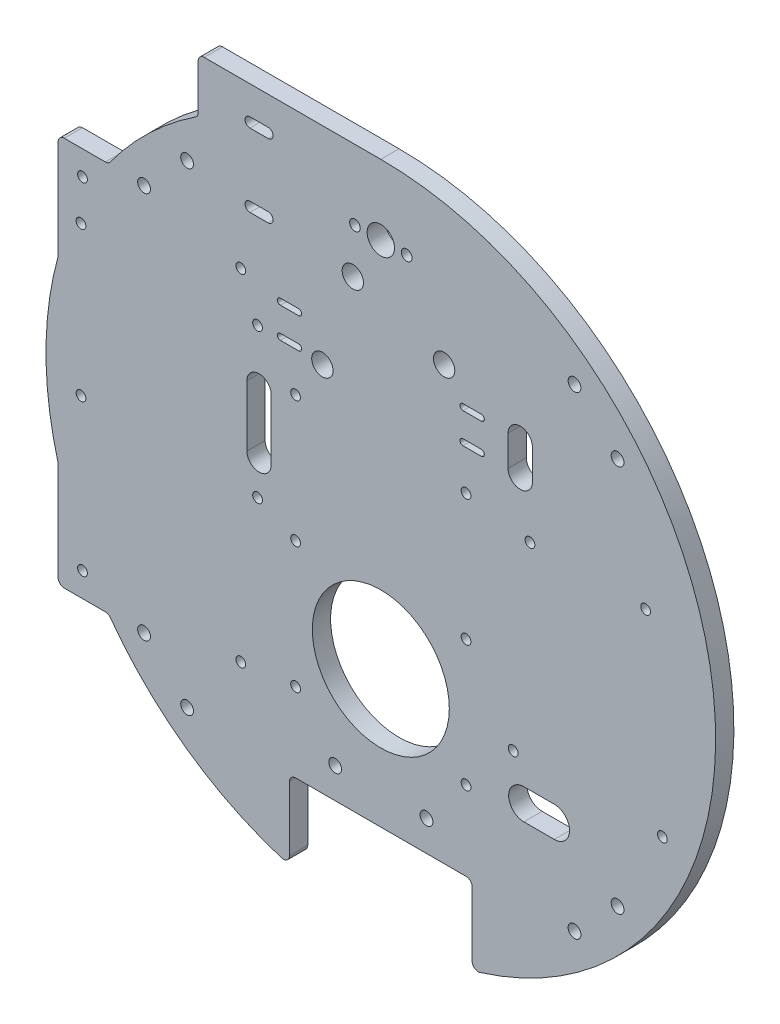
SolidWorks part; units mm, degrees
ref_plane "Plan de face" through (0, 0, 0) normal (0, 0, 1) x (1, 0, 0)
ref_plane "Plan de dessus" through (0, 0, 0) normal (0, 1, 0) x (1, 0, 0)
ref_plane "Plan de droite" through (0, 0, 0) normal (1, 0, 0) x (0, 0, -1)
sketch "Esquisse1" plane through (0, 0, 0) normal (0, 0, 1) x (1, 0, 0)
  line L0 (-30, 0) -> (-30, -25.8301)
  line L1 (-30, 0) -> (30, 0)
  line L5 (30, 0) -> (30, -25.8301)
  line L6 (0, 190) -> (-60, 190)
  line L7 (-60, 190) -> (-60, 172.1954)
  arc A0 (30, -25.8301) -> (0, 190) centre (0, 80) ccw
  arc A1 (-60, 172.1954) -> (-30, -25.8301) centre (0, 80) ccw
  dimension "D4" = 220
  dimension "D1" = 60
  dimension "D2" = 60
  dimension "D3" = 80
extrude "Boss.-Extru.1" add sketch "Esquisse1" along normal blind 6
sketch "Esquisse2" plane through (0, 0, 0) normal (0, 0, 1) x (1, 0, 0)
  line L0 (0, 167) -> (0, 190) construction
  line L2 (-8.5, 167) -> (8.5, 167) construction
  circle A0 centre (28, 26) radius 1.6 construction
  circle A1 centre (-28, 26) radius 1.6 construction
  circle A2 centre (-28, 67.5) radius 1.6 construction
  circle A3 centre (-28, 109) radius 1.6 construction
  circle A4 centre (28, 67.5) radius 1.6 construction
  circle A5 centre (28, 109) radius 1.6 construction
  circle A6 centre (28, 26) radius 1.6
  circle A7 centre (-28, 26) radius 1.6
  circle A8 centre (-28, 67.5) radius 1.6
  circle A9 centre (-28, 109) radius 1.6
  circle A10 centre (28, 67.5) radius 1.6
  circle A11 centre (28, 109) radius 1.6
  circle A12 centre (8.5, 167) radius 1.75
  circle A13 centre (-8.5, 167) radius 1.75
  circle A14 centre (0, 167) radius 4.5
  dimension "D1" = 3.5
  dimension "D3" = 9
  dimension "D2" = 17
extrude "Enlèv. mat.-Extru.1" cut sketch "Esquisse2" along normal blind 10
sketch "Esquisse4" plane through (0, 0, 0) normal (0, 0, 1) x (1, 0, 0)
  circle A3 centre (0, 45) radius 22.5
  dimension "D1" = 45
  dimension "D2" = 45
extrude "Enlèv. mat.-Extru.2" cut sketch "Esquisse4" along normal through all
sketch "Esquisse5" plane through (0, 0, 0) normal (0, 0, -1) x (-1, 0, 0)
  circle A0 centre (15, 10) radius 2.1 construction
  circle A2 centre (15, 10) radius 2.1
extrude "Enlèv. mat.-Extru.4" cut sketch "Esquisse5" against normal through all
mirror "Symétrie1" about plane through (0, 0, 0) normal (1, 0, 0) of "Enlèv. mat.-Extru.4"
fillet "Congé2" radius 2 6 edges at (-30, -25.8301, 3) (-30, 0, 3) (30, 0, 3) (30, -25.8301, 3) (-60, 172.1954, 3) (-60, 190, 3)
sketch "Esquisse6" plane through (0, 0, 6) normal (0, 0, 1) x (1, 0, 0)
  line L0 (-43, 179) -> (-37, 179) construction
  line L1 (-43, 180.6) -> (-37, 180.6)
  line L2 (-43, 177.4) -> (-37, 177.4)
  line L3 (-43, 155) -> (-37, 155) construction
  line L4 (-43, 156.6) -> (-37, 156.6)
  line L5 (-43, 153.4) -> (-37, 153.4)
  line L6 (-42.5102, 167) -> (-70.2302, 167) construction
  arc A0 (-43, 180.6) -> (-43, 177.4) centre (-43, 179) ccw
  arc A1 (-37, 177.4) -> (-37, 180.6) centre (-37, 179) ccw
  arc A2 (-43, 156.6) -> (-43, 153.4) centre (-43, 155) ccw
  arc A3 (-37, 153.4) -> (-37, 156.6) centre (-37, 155) ccw
  point P2 (-40, 179)
  point P8 (-40, 155)
  dimension "D1" = 1.6
  dimension "D2" = 6
  dimension "D3" = 12
  dimension "D4" = 12
  dimension "D5" = 40
extrude "Enlèv. mat.-Extru.5" cut sketch "Esquisse6" against normal up to next
sketch "Esquisse7" plane through (0, 0, 0) normal (0, 0, -1) x (-1, 0, 0)
  line L0 (-77.7817, 157.7817) -> (77.7817, 2.2183) construction
  line L1 (-63.6396, 157.7817) -> (-77.7817, 143.6396) construction
  line L2 (0, 80) -> (-110, 80) construction
  arc A0 (0, 190) -> (-32.5926, -25.0606) centre (0, 80) ccw construction
  arc A1 (32.5926, -25.0606) -> (60.8929, 171.6082) centre (0, 80) ccw construction
  circle A2 centre (-63.6396, 157.7817) radius 2.1
  circle A3 centre (-77.7817, 143.6396) radius 2.1
  arc A4 (0, 190) -> (-32.5926, -25.0606) centre (0, 80) ccw construction
  point P13 (-70.7107, 150.7107)
  point P14 (0, 80)
  dimension "D2" = 4.2
  dimension "D1" = 20
  dimension "D3" = 100
  dimension "D4" = 45
extrude "Enlèv. mat.-Extru.6" cut sketch "Esquisse7" against normal through all
ref_axis "Axe1" through (0, 80, 6) along (0, 0, -1)
pattern_circular "Répétition circulaire1" count 4 over 360 about axis through (0, 80, 6) along (0, 0, -1) of "Enlèv. mat.-Extru.6"
sketch "Esquisse8" plane through (0, 0, 6) normal (0, 0, 1) x (1, 0, 0)
  line L0 (-28, 109) -> (29.6, 109) construction
  line L1 (0.8, 132) -> (0.8, 109) construction
  line L2 (-19.2, 152) -> (20.8, 152) construction
  line L3 (-19.2, 152) -> (-19.2, 112) construction
  line L4 (-19.2, 112) -> (20.8, 112) construction
  line L5 (20.8, 152) -> (20.8, 112) construction
  line L6 (-19.2, 152) -> (20.8, 112) construction
  line L7 (-19.2, 112) -> (20.8, 152) construction
  circle A1 centre (28, 109) radius 1.6 construction
  circle A2 centre (20.8, 142) radius 3.5
  circle A3 centre (-9.2, 152) radius 3.5
  circle A4 centre (-19.2, 122) radius 3.5
  point P6 (0.8, 132)
  dimension "D6" = 7
  dimension "D1" = 3
  dimension "D2" = 40
  dimension "D3" = 10
  dimension "D4" = 10
  dimension "D5" = 10
extrude "Enlèv. mat.-Extru. Relais Mot piston" cut sketch "Esquisse8" against normal through all
sketch "Esquisse14" plane through (0, 0, 0) normal (0, 0, 1) x (1, 0, 0)
  line L0 (-33, 133) -> (-27, 133) construction
  line L1 (-33, 134) -> (-27, 134)
  line L2 (-33, 132) -> (-27, 132)
  line L3 (-33, 123) -> (-27, 123) construction
  line L4 (-33, 124) -> (-27, 124)
  line L5 (-33, 122) -> (-27, 122)
  line L6 (-30, 133) -> (-30, 123) construction
  arc A0 (-33, 134) -> (-33, 132) centre (-33, 133) ccw
  arc A1 (-27, 132) -> (-27, 134) centre (-27, 133) ccw
  arc A2 (-33, 124) -> (-33, 122) centre (-33, 123) ccw
  arc A3 (-27, 122) -> (-27, 124) centre (-27, 123) ccw
  point P2 (-30, 133)
  point P8 (-30, 123)
  point P16 (-30, 128)
  dimension "D1" = 1
  dimension "D2" = 1
  dimension "D3" = 6
  dimension "D4" = 6
  dimension "D5" = 30
  dimension "D6" = 48
  dimension "D7" = 10
extrude "Enlèv. mat.-Extru.8" cut sketch "Esquisse14" along normal through all
mirror "Symétrie3" about plane through (0, 0, 0) normal (1, 0, 0) of "Enlèv. mat.-Extru.8"
sketch "Esquisse9" plane through (0, 0, 0) normal (0, 0, 1) x (1, 0, 0)
  line L0 (-42, 80) -> (0, 80) construction
  line L1 (-102, 140) -> (-42, 140) construction
  line L2 (-102, 140) -> (-102, 20) construction
  line L3 (-102, 20) -> (-42, 20) construction
  line L4 (-42, 140) -> (-42, 20) construction
  line L6 (-106, 144) -> (-106, 109.3939)
  line L7 (-106, 144) -> (-89.4651, 144)
  line L9 (-106, 144) -> (-42, 144) construction
  line L10 (-106, 16) -> (-42, 16) construction
  line L11 (-106, 144) -> (-106, 16) construction
  arc A0 (-60.8929, 171.6082) -> (-32.5926, -25.0606) centre (0, 80) ccw construction
  arc A1 (-89.4651, 144) -> (-106, 109.3939) centre (0, 80) ccw
  dimension "D1" = 120
  dimension "D2" = 60
  dimension "D3" = 42
  dimension "D4" = 4
extrude "Boss.-Extru.2" add sketch "Esquisse9" along normal blind 6
sketch "Esquisse15" plane through (0, 0, 6) normal (0, 0, 1) x (1, 0, 0)
  line L0 (45.8, 133) -> (45.8, 123) construction
  line L1 (49.8, 133) -> (49.8, 123)
  line L2 (41.8, 133) -> (41.8, 123)
  line L3 (45.8, 128) -> (21.9026, 128) construction
  line L5 (27, 134) -> (33, 134) construction
  line L6 (33, 122) -> (27, 122) construction
  line L7 (0.8, 132) -> (0.8, 109) construction
  arc A0 (49.8, 133) -> (41.8, 133) centre (45.8, 133) ccw
  arc A1 (41.8, 123) -> (49.8, 123) centre (45.8, 123) ccw
  point P2 (45.8, 128)
  dimension "D1" = 4
  dimension "D2" = 10
  dimension "D3" = 45
extrude "Enlèv. mat.-Extru.9" cut sketch "Esquisse15" against normal through all
fillet "Congé3" radius 2 3 edges at (-106, 144, 3) (-106, 109.3939, 3) (-89.4651, 144, 3)
sketch "Esquisse10" plane through (0, 0, 0) normal (0, 0, 1) x (1, 0, 0)
  line L0 (-102, 140) -> (-42, 140) construction
  line L2 (-102, 140) -> (-102, 20) construction
  line L3 (-72, 140) -> (-72, 113.3247) construction
  circle A0 centre (-46, 136) radius 1.6
  circle A1 centre (-98, 136) radius 1.6
  dimension "D2" = 3.2
  dimension "D1" = 4
  dimension "D3" = 4
extrude "Enlèv. mat.-Extru. Pont H Mot caisses" cut sketch "Esquisse10" along normal through all
ref_plane "Plan1" through (0, 80, 0) normal (0, 1, 0) x (1, 0, 0)
mirror "Symétrie2" about plane through (0, 80, 0) normal (0, 1, 0) of "Enlèv. mat.-Extru. Pont H Mot caisses", "Congé3", "Boss.-Extru.2"
sketch "Esquisse13" plane through (0, 0, 6) normal (0, 0, 1) x (1, 0, 0)
  line L0 (-40, 85) -> (-40, 105) construction
  line L1 (-44, 85) -> (-44, 105)
  line L2 (-36, 85) -> (-36, 105)
  arc A0 (-44, 85) -> (-36, 85) centre (-40, 85) ccw
  arc A1 (-36, 105) -> (-44, 105) centre (-40, 105) ccw
  point P2 (-40, 95)
  dimension "D2" = 4
  dimension "D1" = 20
  dimension "D3" = 40
  dimension "D4" = 15
extrude "Enlèv. mat.-Extru.7" cut sketch "Esquisse13" against normal through all
sketch "Esquisse11" plane through (0, 0, 6) normal (0, 0, 1) x (1, 0, 0)
  line L1 (-122, 126) -> (-37, 126) construction
  line L2 (-122, 126) -> (-122, 70) construction
  line L3 (-122, 70) -> (-37, 70) construction
  line L4 (-37, 126) -> (-37, 70) construction
  line L5 (-122, 126) -> (-37, 70) construction
  line L6 (-122, 70) -> (-37, 126) construction
  line L7 (-98.5, 122.5) -> (-40.5, 122.5) construction
  line L8 (-40.5, 122.5) -> (-40.5, 73.5) construction
  line L9 (-40.5, 73.5) -> (-98.5, 73.5) construction
  line L10 (-98.5, 73.5) -> (-98.5, 122.5) construction
  line L11 (-40.5, 98) -> (-37, 98) construction
  circle A0 centre (-40.5, 73.5) radius 1.6
  circle A1 centre (-98.5, 73.5) radius 1.6
  circle A2 centre (-40.5, 122.5) radius 1.6
  circle A3 centre (-98.5, 122.5) radius 1.6
  point P0 (-79.5, 98)
  dimension "D6" = 3.2
  dimension "D8" = 18
  dimension "D1" = 85
  dimension "D2" = 56
  dimension "D3" = 37
  dimension "D4" = 58
  dimension "D5" = 49
  dimension "D7" = 3.5
extrude "Enlèv. mat.-Extru. Raspberry" cut sketch "Esquisse11" against normal through all
sketch "Esquisse12" plane through (0, 0, 6) normal (0, 0, 1) x (1, 0, 0)
  line L0 (0, 80) -> (110, 80) construction
  line L1 (43.5, 43.5) -> (92.5, 43.5) construction
  line L2 (39.5, 120.5) -> (96.5, 120.5) construction
  line L3 (39.5, 120.5) -> (39.5, 39.5) construction
  line L4 (39.5, 39.5) -> (96.5, 39.5) construction
  line L5 (96.5, 120.5) -> (96.5, 39.5) construction
  line L6 (39.5, 120.5) -> (96.5, 39.5) construction
  line L7 (39.5, 39.5) -> (96.5, 120.5) construction
  line L8 (49, 105.5) -> (87, 105.5) construction
  line L9 (68, 105.5) -> (68, 43.5) construction
  line L10 (47, 30) -> (57, 30) construction
  line L11 (47, 35) -> (57, 35)
  line L12 (47, 25) -> (57, 25)
  arc A0 (32.5926, -25.0606) -> (0, 190) centre (0, 80) ccw construction
  circle A1 centre (43.5, 43.5) radius 1.6
  circle A2 centre (92.5, 43.5) radius 1.6
  circle A3 centre (49, 105.5) radius 1.6
  circle A4 centre (87, 105.5) radius 1.6
  arc A5 (47, 35) -> (47, 25) centre (47, 30) ccw
  arc A6 (57, 25) -> (57, 35) centre (57, 30) ccw
  point P7 (68, 80)
  point P24 (52, 30)
  dimension "D6" = 3.2
  dimension "D10" = 5
  dimension "D1" = 57
  dimension "D2" = 81
  dimension "D3" = 68
  dimension "D4" = 49
  dimension "D5" = 4
  dimension "D7" = 38
  dimension "D8" = 62
  dimension "D9" = 10
  dimension "D11" = 52
  dimension "D12" = 50
extrude "Enlèv. mat.-Extru. Arduino" cut sketch "Esquisse12" against normal through all
